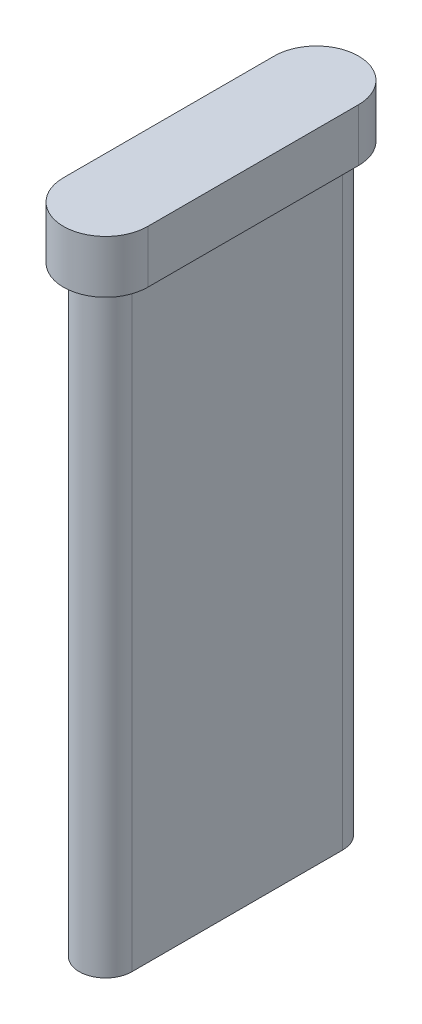
SolidWorks part; units mm, degrees
material "K110"
ref_plane "Front Plane" through (0, 0, 0) normal (0, 0, 1) x (1, 0, 0)
ref_plane "Top Plane" through (0, 0, 0) normal (0, 1, 0) x (1, 0, 0)
ref_plane "Right Plane" through (0, 0, 0) normal (1, 0, 0) x (0, 0, -1)
sketch "Sketch1" plane through (0, 0, 0) normal (0, 1, 0) x (1, 0, 0)
  line L0 (0, -10) -> (0, 10) construction
  line L1 (-2.5, -10) -> (-2.5, 10)
  line L2 (2.5, -10) -> (2.5, 10)
  arc A0 (-2.5, -10) -> (2.5, -10) centre (0, -10) ccw
  arc A1 (2.5, 10) -> (-2.5, 10) centre (0, 10) ccw
  point P2 (0, 0)
  dimension "D2" = 2.5
  dimension "D1" = 20
extrude "Boss-Extrude1" add sketch "Sketch1" against normal blind 62
sketch "Sketch2" plane through (0, 0, 0) normal (0, 1, 0) x (1, 0, 0)
  line L4 (4, -10) -> (4, 10)
  line L5 (-4, 10) -> (-4, -10)
  line L6 (4, -10) -> (4, 10)
  line L7 (-4, 10) -> (-4, -10)
  arc A4 (4, 10) -> (-4, 10) centre (0, 10) ccw
  arc A5 (-4, -10) -> (4, -10) centre (0, -10) ccw
  arc A6 (4, 10) -> (-4, 10) centre (0, 10) ccw
  arc A7 (-4, -10) -> (4, -10) centre (0, -10) ccw
  dimension "D1" = 1.5
extrude "Boss-Extrude2" add sketch "Sketch2" against normal blind 5
